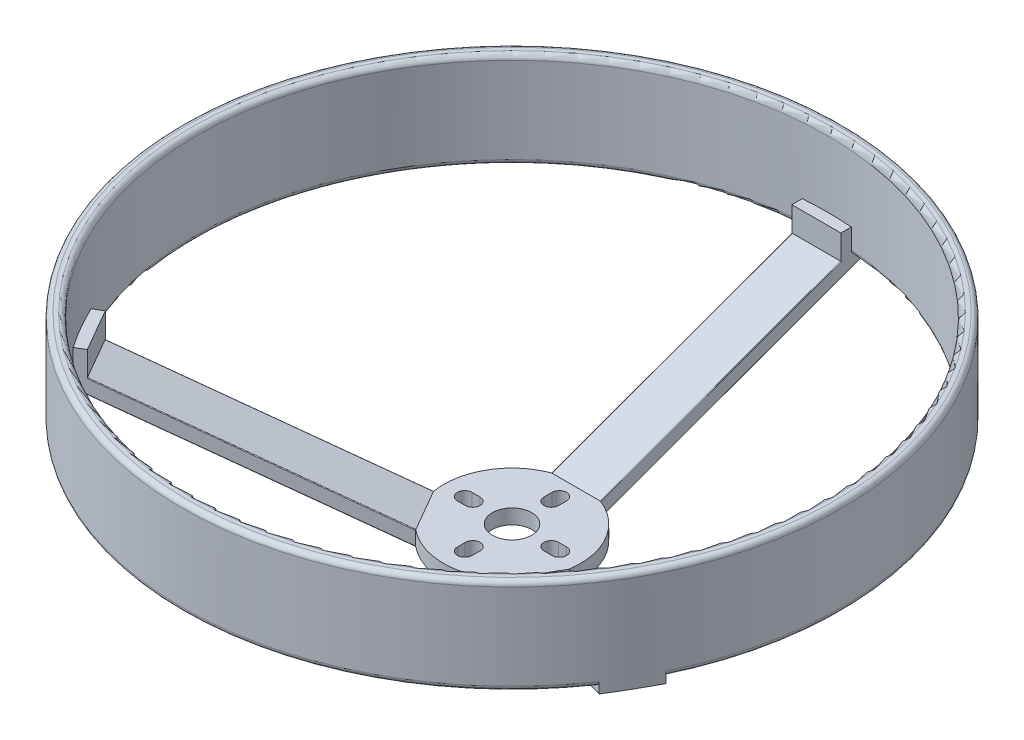
SolidWorks part; units mm, degrees
note: '?' marks a value the reader was unsure of.
ref_plane "Front Plane" through (0, 0, 0) normal (0, 0, 1) x (1, 0, 0)
ref_plane "Top Plane" through (0, 0, 0) normal (0, 1, 0) x (1, 0, 0)
ref_plane "Right Plane" through (0, 0, 0) normal (1, 0, 0) x (0, 0, -1)
sketch "Sketch1" plane through (0, 0, 0) normal (0, 1, 0) x (1, 0, 0)
  circle A0 centre (0, 0) radius 13.95
  dimension "D1" = 27.9
extrude "Boss-Extrude1" add sketch "Sketch1" along normal mid plane 3
sketch "Sketch2" plane through (0, 1.5, 0) normal (0, 1, 0) x (1, 0, 0)
  circle A0 centre (0, 0) radius 4
  dimension "D1" = 8
extrude "Cut-Extrude1" cut sketch "Sketch2" against normal through all
sketch "Sketch3" plane through (0, 1.5, 0) normal (0, 1, 0) x (1, 0, 0)
  line L0 (-5, 13.0232) -> (5, 13.0232)
  line L1 (0, 0) -> (45.3875, -26.2045) construction
  line L2 (-54.6669, 0) -> (58.4687, 0) construction
  line L3 (13.7784, -2.1814) -> (8.7784, -10.8417)
  line L4 (0, -45.9228) -> (0, 39.2694) construction
  line L5 (-13.7784, -2.1814) -> (-8.7784, -10.8417)
  line L6 (8.7784, -10.8417) -> (17.4386, -15.8417)
  line L7 (17.4386, -15.8417) -> (22.4386, -7.1814)
  line L8 (22.4386, -7.1814) -> (13.7784, -2.1814)
  line L9 (-5, 13.0232) -> (-5, 23.0232)
  line L10 (-5, 23.0232) -> (5, 23.0232)
  line L11 (5, 23.0232) -> (5, 13.0232)
  line L12 (-8.7784, -10.8417) -> (-17.4386, -15.8417)
  line L13 (-17.4386, -15.8417) -> (-22.4386, -7.1814)
  line L14 (-22.4386, -7.1814) -> (-13.7784, -2.1814)
  circle A0 centre (0, 0) radius 13.95 construction
  circle A3 centre (-9.63, 0) radius 1.5
  circle A4 centre (0, -8) radius 1.5
  circle A5 centre (0, 8) radius 1.5
  circle A6 centre (9.63, 0) radius 1.5
  dimension "D7" = 3
  dimension "D1" = 10
  dimension "D2" = 30
  dimension "D3" = 10
  dimension "D4" = 10
  dimension "D5" = 10
  dimension "D6" = 10
  dimension "D8" = 9.63
  dimension "D9" = 8
  dimension "D10" = 9.63
  dimension "D11" = 8
extrude "Cut-Extrude2" cut sketch "Sketch3" against normal through all
ref_axis "Axis1" through (0, -18.5837, 0) along (0, 1, 0)?
sketch "Sketch4" plane through (0, 0, 0) normal (1, 0, 0) x (0, 0, -1)
  line L0 (13.0232, -1.5) -> (82.6029, 23.825)
  line L1 (13.0232, -1.5) -> (84.4437, -1.5) construction
  dimension "D1" = 20
sketch "Sketch5" plane through (0, 0, -13.0232) normal (0, 0, -1) x (-1, 0, 0)
  line L4 (5, 1.5) -> (-5, 1.5)
  line L5 (-5, 1.5) -> (-5, -1.5)
  line L6 (-5, -1.5) -> (5, -1.5)
  line L8 (5, 1.5) -> (-5, 1.5)
  line L10 (-5, -1.5) -> (5, -1.5)
  line L12 (-5, 1.5) -> (-5, -1.5)
  line L14 (5, -1.5) -> (5, 1.5)
  line L15 (5, -1.5) -> (5, 1.5)
  dimension "D1" = 0
sweep "Sweep1" add profiles "Sketch5" path "Sketch4"
pattern_circular "CirPattern1" count 3 every 120 about axis through (0, 0, 0) along (0, 1, 0) of "Sweep1"
ref_plane "Plane1" through (0, 26.825, 0) normal (0, 1, 0) x (1, 0, 0)
sketch "Sketch6" plane through (0, 26.825, 0) normal (0, 1, 0) x (1, 0, 0)
  circle A0 centre (0, 0) radius 100
  dimension "D2" = 200
extrude "Cut-Extrude3" cut sketch "Sketch6" against normal blind 7.5
sketch "Sketch7" plane through (0, 19.325, 0) normal (0, 1, 0) x (1, 0, 0)
  circle A0 centre (0, 0) radius 70
  circle A1 centre (0, 0) radius 64.31
  dimension "D1" = 140
  dimension "D2" = 128.62
extrude "Boss-Extrude2" add sketch "Sketch7" along normal blind 7
sketch "Sketch8" plane through (0, 19.325, 0) normal (0, 1, 0) x (1, 0, 0)
  line L12 (-62.9669, -30.5805) -> (-63.329, -30.7895) construction
  line L13 (-63.329, -30.7895) -> (-58.329, -39.4498) construction
  line L14 (-58.329, -39.4498) -> (-57.9669, -39.2407) construction
  line L15 (-56.1909, -26.6683) -> (-58.0255, -27.7275) construction
  line L16 (-53.0255, -36.3878) -> (-51.1909, -35.3286) construction
  line L17 (-51.1909, -35.3286) -> (-56.1909, -26.6683) construction
  line L18 (5, 61.9969) -> (5, 64.1153) construction
  line L19 (-5, 64.1153) -> (-5, 61.9969) construction
  line L20 (-5, 61.9969) -> (5, 61.9969) construction
  line L21 (5, 69.8212) -> (5, 70.2393) construction
  line L22 (5, 70.2393) -> (-5, 70.2393) construction
  line L23 (-5, 70.2393) -> (-5, 69.8212) construction
  line L24 (57.9669, -39.2407) -> (58.329, -39.4498) construction
  line L25 (58.329, -39.4498) -> (63.329, -30.7895) construction
  line L26 (63.329, -30.7895) -> (62.9669, -30.5805) construction
  line L27 (51.1909, -35.3286) -> (53.0255, -36.3878) construction
  line L28 (58.0255, -27.7275) -> (56.1909, -26.6683) construction
  line L29 (56.1909, -26.6683) -> (51.1909, -35.3286) construction
  line L30 (-62.9669, -30.5805) -> (-63.329, -30.7895)
  line L31 (-63.329, -30.7895) -> (-58.329, -39.4498)
  line L32 (-58.329, -39.4498) -> (-57.9669, -39.2407)
  line L33 (-56.1909, -26.6683) -> (-58.0255, -27.7275)
  line L34 (-53.0255, -36.3878) -> (-51.1909, -35.3286)
  line L35 (-51.1909, -35.3286) -> (-56.1909, -26.6683)
  line L36 (5, 61.9969) -> (5, 64.1153)
  line L37 (-5, 64.1153) -> (-5, 61.9969)
  line L38 (-5, 61.9969) -> (5, 61.9969)
  line L39 (5, 69.8212) -> (5, 70.2393)
  line L40 (5, 70.2393) -> (-5, 70.2393)
  line L41 (-5, 70.2393) -> (-5, 69.8212)
  line L42 (57.9669, -39.2407) -> (58.329, -39.4498)
  line L43 (58.329, -39.4498) -> (63.329, -30.7895)
  line L44 (63.329, -30.7895) -> (62.9669, -30.5805)
  line L45 (51.1909, -35.3286) -> (53.0255, -36.3878)
  line L46 (58.0255, -27.7275) -> (56.1909, -26.6683)
  line L47 (56.1909, -26.6683) -> (51.1909, -35.3286)
  arc A4 (-62.9669, -30.5805) -> (-57.9669, -39.2407) centre (0, 0) ccw construction
  arc A5 (-58.0255, -27.7275) -> (-53.0255, -36.3878) centre (0, 0) ccw construction
  arc A6 (5, 64.1153) -> (-5, 64.1153) centre (0, 0) ccw construction
  arc A7 (5, 69.8212) -> (-5, 69.8212) centre (0, 0) ccw construction
  arc A8 (57.9669, -39.2407) -> (62.9669, -30.5805) centre (0, 0) ccw construction
  arc A9 (53.0255, -36.3878) -> (58.0255, -27.7275) centre (0, 0) ccw construction
  arc A10 (-62.9669, -30.5805) -> (-57.9669, -39.2407) centre (0, 0) ccw
  arc A11 (-58.0255, -27.7275) -> (-53.0255, -36.3878) centre (0, 0) ccw
  arc A12 (5, 64.1153) -> (-5, 64.1153) centre (0, 0) ccw
  arc A13 (5, 69.8212) -> (-5, 69.8212) centre (0, 0) ccw
  arc A14 (57.9669, -39.2407) -> (62.9669, -30.5805) centre (0, 0) ccw
  arc A15 (53.0255, -36.3878) -> (58.0255, -27.7275) centre (0, 0) ccw
extrude "Boss-Extrude3" add sketch "Sketch8" along normal up to surface (7 mm away) up to face at (-70, 26.325, 0)
fillet "Fillet2" radius 0.125 12 edges at (-5, 10.4125, -37.51) (5, 10.4125, -37.51) (5, 8.9125, -41.6312) (-5, 8.9125, -41.6312) (-29.9846, 10.4125, 23.0851) (-34.9846, 10.4125, 14.4249) (-38.5537, 8.9125, 16.4855) (-33.5537, 8.9125, 25.1457) (34.9846, 10.4125, 14.4249) (29.9846, 10.4125, 23.0851) (33.5537, 8.9125, 25.1457) (38.5537, 8.9125, 16.4855)
sketch "Sketch13" plane through (0, 26.325, 0) normal (0, 1, 0) x (1, 0, 0)
  line L9 (57.9669, -39.2407) -> (58.329, -39.4498)
  line L10 (58.329, -39.4498) -> (63.329, -30.7895)
  line L11 (63.329, -30.7895) -> (62.9669, -30.5805)
  line L12 (5, 69.8212) -> (5, 70.2393)
  line L13 (5, 70.2393) -> (-5, 70.2393)
  line L14 (-5, 70.2393) -> (-5, 69.8212)
  line L15 (-62.9669, -30.5805) -> (-63.329, -30.7895)
  line L16 (-63.329, -30.7895) -> (-58.329, -39.4498)
  line L17 (-58.329, -39.4498) -> (-57.9669, -39.2407)
  line L18 (57.9669, -39.2407) -> (58.329, -39.4498)
  line L19 (58.329, -39.4498) -> (63.329, -30.7895)
  line L20 (63.329, -30.7895) -> (62.9669, -30.5805)
  line L21 (5, 69.8212) -> (5, 70.2393)
  line L22 (5, 70.2393) -> (-5, 70.2393)
  line L23 (-5, 70.2393) -> (-5, 69.8212)
  line L24 (-62.9669, -30.5805) -> (-63.329, -30.7895)
  line L25 (-63.329, -30.7895) -> (-58.329, -39.4498)
  line L26 (-58.329, -39.4498) -> (-57.9669, -39.2407)
  circle A0 centre (0, 0) radius 64.31
  arc A3 (-57.9669, -39.2407) -> (57.9669, -39.2407) centre (0, 0) ccw
  arc A4 (62.9669, -30.5805) -> (5, 69.8212) centre (0, 0) ccw
  arc A5 (-5, 69.8212) -> (-62.9669, -30.5805) centre (0, 0) ccw
  arc A6 (-57.9669, -39.2407) -> (57.9669, -39.2407) centre (0, 0) ccw
  arc A7 (62.9669, -30.5805) -> (5, 69.8212) centre (0, 0) ccw
  arc A8 (-5, 69.8212) -> (-62.9669, -30.5805) centre (0, 0) ccw
  line M26 (-53.0255, -36.3878) -> (-51.1909, -35.3286)
  line M27 (-51.1909, -35.3286) -> (-56.1909, -26.6683)
  line M28 (-56.1909, -26.6683) -> (-58.0255, -27.7275)
  line M30 (-5, 64.1153) -> (-5, 61.9969)
  line M31 (-5, 61.9969) -> (5, 61.9969)
  line M32 (5, 61.9969) -> (5, 64.1153)
  line M34 (58.0255, -27.7275) -> (56.1909, -26.6683)
  line M35 (56.1909, -26.6683) -> (51.1909, -35.3286)
  line M36 (51.1909, -35.3286) -> (53.0255, -36.3878)
  dimension "D1" = 0
extrude "Cut-Extrude4" cut sketch "Sketch13" against normal blind 7 contours A0 M32 M30 M31 | A0 M36 M34 M35 | A0 M28 M26 M27
sketch "Sketch14" plane through (0, 26.325, 0) normal (0, 1, 0) x (1, 0, 0)
  line L9 (57.9669, -39.2407) -> (58.329, -39.4498)
  line L10 (58.329, -39.4498) -> (63.329, -30.7895)
  line L11 (63.329, -30.7895) -> (62.9669, -30.5805)
  line L12 (5, 69.8212) -> (5, 70.2393)
  line L13 (5, 70.2393) -> (-5, 70.2393)
  line L14 (-5, 70.2393) -> (-5, 69.8212)
  line L15 (-62.9669, -30.5805) -> (-63.329, -30.7895)
  line L16 (-63.329, -30.7895) -> (-58.329, -39.4498)
  line L17 (-58.329, -39.4498) -> (-57.9669, -39.2407)
  line L18 (57.9669, -39.2407) -> (58.329, -39.4498)
  line L19 (58.329, -39.4498) -> (63.329, -30.7895)
  line L20 (63.329, -30.7895) -> (62.9669, -30.5805)
  line L21 (5, 69.8212) -> (5, 70.2393)
  line L22 (5, 70.2393) -> (-5, 70.2393)
  line L23 (-5, 70.2393) -> (-5, 69.8212)
  line L24 (-62.9669, -30.5805) -> (-63.329, -30.7895)
  line L25 (-63.329, -30.7895) -> (-58.329, -39.4498)
  line L26 (-58.329, -39.4498) -> (-57.9669, -39.2407)
  circle A0 centre (0, 0) radius 67.13
  arc A3 (-57.9669, -39.2407) -> (57.9669, -39.2407) centre (0, 0) ccw
  arc A4 (62.9669, -30.5805) -> (5, 69.8212) centre (0, 0) ccw
  arc A5 (-5, 69.8212) -> (-62.9669, -30.5805) centre (0, 0) ccw
  arc A6 (-57.9669, -39.2407) -> (57.9669, -39.2407) centre (0, 0) ccw
  arc A7 (62.9669, -30.5805) -> (5, 69.8212) centre (0, 0) ccw
  arc A8 (-5, 69.8212) -> (-62.9669, -30.5805) centre (0, 0) ccw
  arc M14 (-57.9669, -39.2407) -> (57.9669, -39.2407) centre (0, 0) ccw
  line M15 (57.9669, -39.2407) -> (58.329, -39.4498)
  line M16 (58.329, -39.4498) -> (63.329, -30.7895)
  line M17 (63.329, -30.7895) -> (62.9669, -30.5805)
  arc M18 (62.9669, -30.5805) -> (5, 69.8212) centre (0, 0) ccw
  line M19 (5, 69.8212) -> (5, 70.2393)
  line M20 (5, 70.2393) -> (-5, 70.2393)
  line M21 (-5, 70.2393) -> (-5, 69.8212)
  arc M22 (-5, 69.8212) -> (-62.9669, -30.5805) centre (0, 0) ccw
  line M23 (-62.9669, -30.5805) -> (-63.329, -30.7895)
  line M24 (-63.329, -30.7895) -> (-58.329, -39.4498)
  line M25 (-58.329, -39.4498) -> (-57.9669, -39.2407)
  dimension "D1" = 0
extrude "Cut-Extrude5" cut sketch "Sketch14" against normal through all both and the other way through all contours A0 M25 M14 M15 M16 M17 M18 M19 M20 M21 M22 M23 M24
sketch "Sketch15" plane through (0, 26.325, 0) normal (0, 1, 0) x (1, 0, 0)
  circle A1 centre (0, 0) radius 67.13
  circle A2 centre (0, 0) radius 67.13
  circle M2 centre (0, 0) radius 64.31
  circle M3 centre (0, 0) radius 67.13
  dimension "D1" = 0
extrude "Boss-Extrude4" add sketch "Sketch15" along normal blind 12.5 contours M3 M2
sketch "Sketch16" plane through (0, 19.325, 0) normal (0, 1, 0) x (1, 0, 0)
  line L0 (-56.1909, -26.6683) -> (-58.0255, -27.7275) construction
  line L1 (-53.0255, -36.3878) -> (-51.1909, -35.3286) construction
  line L2 (-51.1909, -35.3286) -> (-51.2534, -35.2203) construction
  line L3 (-51.2534, -35.2203) -> (-56.1284, -26.7766) construction
  line L4 (-56.1284, -26.7766) -> (-56.1909, -26.6683) construction
  line L5 (51.1909, -35.3286) -> (53.0255, -36.3878) construction
  line L6 (58.0255, -27.7275) -> (56.1909, -26.6683) construction
  line L7 (56.1909, -26.6683) -> (56.1284, -26.7766) construction
  line L8 (56.1284, -26.7766) -> (51.2534, -35.2203) construction
  line L9 (51.2534, -35.2203) -> (51.1909, -35.3286) construction
  line L10 (5, 61.9969) -> (5, 64.1153) construction
  line L11 (-5, 64.1153) -> (-5, 61.9969) construction
  line L12 (-5, 61.9969) -> (-4.875, 61.9969) construction
  line L13 (-4.875, 61.9969) -> (4.875, 61.9969) construction
  line L14 (4.875, 61.9969) -> (5, 61.9969) construction
  line L15 (-56.1909, -26.6683) -> (-58.0255, -27.7275)
  line L16 (-53.0255, -36.3878) -> (-51.1909, -35.3286)
  line L17 (-51.1909, -35.3286) -> (-51.2534, -35.2203)
  line L18 (-51.2534, -35.2203) -> (-56.1284, -26.7766)
  line L19 (-56.1284, -26.7766) -> (-56.1909, -26.6683)
  line L20 (51.1909, -35.3286) -> (53.0255, -36.3878)
  line L21 (58.0255, -27.7275) -> (56.1909, -26.6683)
  line L22 (56.1909, -26.6683) -> (56.1284, -26.7766)
  line L23 (56.1284, -26.7766) -> (51.2534, -35.2203)
  line L24 (51.2534, -35.2203) -> (51.1909, -35.3286)
  line L25 (5, 61.9969) -> (5, 64.1153)
  line L26 (-5, 64.1153) -> (-5, 61.9969)
  line L27 (-5, 61.9969) -> (-4.875, 61.9969)
  line L28 (-4.875, 61.9969) -> (4.875, 61.9969)
  line L29 (4.875, 61.9969) -> (5, 61.9969)
  arc A0 (-58.0255, -27.7275) -> (-53.0255, -36.3878) centre (0, 0) ccw construction
  arc A1 (53.0255, -36.3878) -> (58.0255, -27.7275) centre (0, 0) ccw construction
  arc A2 (5, 64.1153) -> (-5, 64.1153) centre (0, 0) ccw construction
  arc A3 (-58.0255, -27.7275) -> (-53.0255, -36.3878) centre (0, 0) ccw
  arc A4 (53.0255, -36.3878) -> (58.0255, -27.7275) centre (0, 0) ccw
  arc A5 (5, 64.1153) -> (-5, 64.1153) centre (0, 0) ccw
extrude "Boss-Extrude5" add sketch "Sketch16" along normal blind 5
fillet "Fillet3" radius 1 2 edges at (-67.13, 38.825, 0) (-64.31, 38.825, 0)
fillet "Fillet4" radius 1 6 edges at (0, 19.325, 64.31) (0, 19.325, 67.13) (58.1363, 19.325, -33.565) (55.6941, 19.325, -32.155) (-55.6941, 19.325, -32.155) (-58.1363, 19.325, -33.565)
sketch "Sketch17" plane through (0, 1.5, 0) normal (0, 1, 0) x (1, 0, 0)
  line L0 (-9.63, -1.5) -> (-9.63, 1.5) construction
  line L1 (-11.13, 0) -> (-8.13, 0) construction
  line L2 (0, -9.5) -> (0, -6.5) construction
  line L3 (4.875, 13.0232) -> (-4.875, 13.0232)
  line L4 (-13.7159, -2.2897) -> (-8.8409, -10.7335)
  line L5 (8.8409, -10.7335) -> (13.7159, -2.2897)
  line L6 (4.875, 13.0232) -> (-4.875, 13.0232)
  line L7 (-13.7159, -2.2897) -> (-8.8409, -10.7335)
  line L8 (8.8409, -10.7335) -> (13.7159, -2.2897)
  line L9 (-1.5, -8) -> (1.5, -8) construction
  line L10 (-1.5, -9.63) -> (-1.4986, -8.0656)
  line L11 (1.5, -9.63) -> (1.5, -8)
  line L12 (8, 1.5) -> (9.63, 1.5)
  line L13 (8, -1.5) -> (9.63, -1.5)
  line L14 (-1.5, 8) -> (-1.5, 9.63)
  line L15 (1.5, 9.63) -> (1.5, 8)
  line L16 (-8, -1.5) -> (-9.63, -1.5)
  line L17 (-8, 1.5) -> (-9.63, 1.5)
  circle A0 centre (-9.63, 0) radius 1.5 construction
  circle A1 centre (-9.63, 0) radius 1.5
  circle A2 centre (0, 9.63) radius 1.5
  arc A3 (-4.9238, 13.0522) -> (-13.7654, -2.2619) centre (0, 0) ccw
  arc A4 (-8.8416, -10.7902) -> (8.8416, -10.7902) centre (0, 0) ccw
  arc A5 (13.7654, -2.2619) -> (4.9238, 13.0522) centre (0, 0) ccw
  arc A6 (-4.9238, 13.0522) -> (-13.7654, -2.2619) centre (0, 0) ccw
  arc A7 (-8.8416, -10.7902) -> (8.8416, -10.7902) centre (0, 0) ccw
  arc A8 (13.7654, -2.2619) -> (4.9238, 13.0522) centre (0, 0) ccw
  circle A9 centre (9.63, 0) radius 1.5
  circle A10 centre (0, -9.63) radius 1.5
  circle A11 centre (0, -8) radius 1.5 construction
  circle A12 centre (0, -8) radius 1.5
  circle A13 centre (-8, 0) radius 1.5
  circle A14 centre (0, 8) radius 1.5
  circle A15 centre (8, 0) radius 1.5
  ellipse E6 centre (-4.875, 13.3886) end of major axis (-4.875, 13.7541) minor radius 0.125 (-4.9238, 13.0522) -> (-4.875, 13.0232) ccw
  ellipse E7 centre (-14.0324, -2.4724) end of major axis (-14.3489, -2.6552) minor radius 0.125 (-13.7159, -2.2897) -> (-13.7654, -2.2619) ccw
  ellipse E8 centre (-9.1574, -10.9162) end of major axis (-9.4739, -11.0989) minor radius 0.125 (-8.8416, -10.7902) -> (-8.8409, -10.7335) ccw
  ellipse E9 centre (9.1574, -10.9162) end of major axis (9.4739, -11.0989) minor radius 0.125 (8.8409, -10.7335) -> (8.8416, -10.7902) ccw
  ellipse E10 centre (14.0324, -2.4724) end of major axis (14.3489, -2.6552) minor radius 0.125 (13.7654, -2.2619) -> (13.7159, -2.2897) ccw
  ellipse E11 centre (4.875, 13.3886) end of major axis (4.875, 13.7541) minor radius 0.125 (4.875, 13.0232) -> (4.9238, 13.0522) ccw
  ellipse E12 centre (-4.875, 13.3886) end of major axis (-4.875, 13.7541) minor radius 0.125 (-4.9238, 13.0522) -> (-4.875, 13.0232) ccw
  ellipse E13 centre (-14.0324, -2.4724) end of major axis (-14.3489, -2.6552) minor radius 0.125 (-13.7159, -2.2897) -> (-13.7654, -2.2619) ccw
  ellipse E14 centre (-9.1574, -10.9162) end of major axis (-9.4739, -11.0989) minor radius 0.125 (-8.8416, -10.7902) -> (-8.8409, -10.7335) ccw
  ellipse E15 centre (9.1574, -10.9162) end of major axis (9.4739, -11.0989) minor radius 0.125 (8.8409, -10.7335) -> (8.8416, -10.7902) ccw
  ellipse E16 centre (14.0324, -2.4724) end of major axis (14.3489, -2.6552) minor radius 0.125 (13.7654, -2.2619) -> (13.7159, -2.2897) ccw
  ellipse E17 centre (4.875, 13.3886) end of major axis (4.875, 13.7541) minor radius 0.125 (4.875, 13.0232) -> (4.9238, 13.0522) ccw
  point P33 (0, 0)
  point P56 (0, 0)
  circle M28 centre (9.63, 0) radius 1.5
  circle M29 centre (0, 8) radius 1.5
  circle M30 centre (-9.63, 0) radius 1.5
  circle M31 centre (0, -8) radius 1.5
  dimension "D1" = 0
  dimension "D2" = 4
  dimension "D3" = 4
extrude "Cut-Extrude6" cut sketch "Sketch17" against normal through all both and the other way through all contours A13 A1 | A13 L16 M30 | A13 L17 M30 | A10 L11 M31 | A10 L10 M31 | A10 M31 | A2 L14 M29 | A2 M29 | A2 L15 M29 | A15 L13 M28 | A15 A9 | A15 L12 M28
